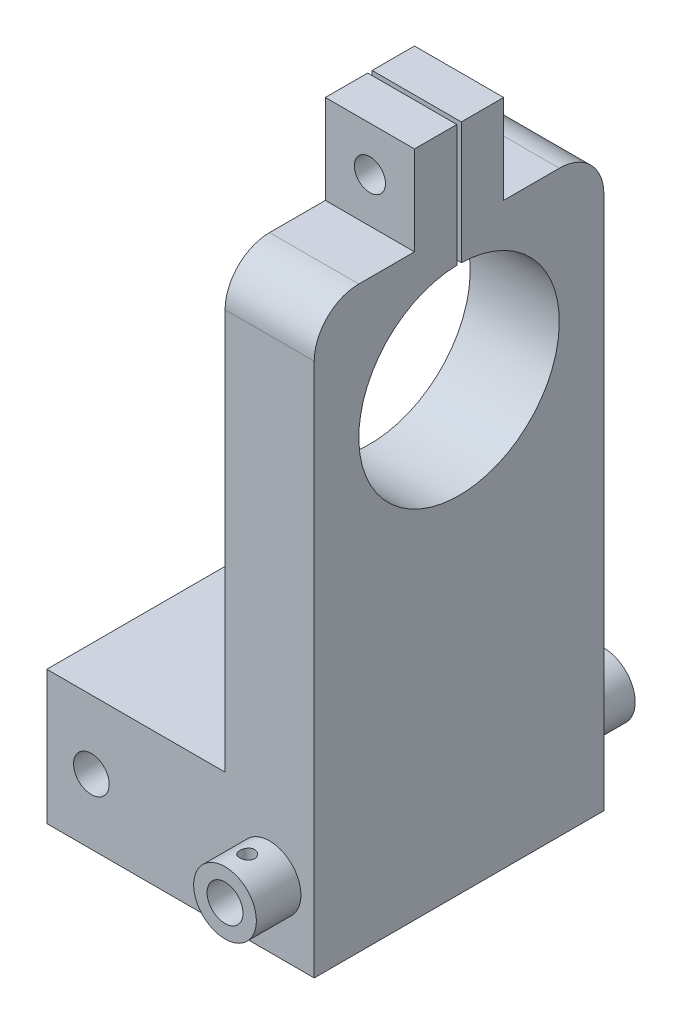
SolidWorks part; units mm, degrees
material "Aleación 6061"
ref_plane "Alzado" through (0, 0, 0) normal (0, 0, 1) x (1, 0, 0)
ref_plane "Planta" through (0, 0, 0) normal (0, 1, 0) x (1, 0, 0)
ref_plane "Vista lateral" through (0, 0, 0) normal (1, 0, 0) x (0, 0, -1)
sketch "Croquis1" plane through (0, 0, 0) normal (1, 0, 0) x (0, 0, -1)
  line L0 (0, 0) -> (0, 49.8635) construction
  line L2 (-32.5, 0) -> (-32.5, -100)
  line L3 (-32.5, -100) -> (32.5, -100)
  line L4 (32.5, 0) -> (32.5, -100)
  line L5 (-32.5, 0) -> (32.5, -100) construction
  line L6 (-32.5, -100) -> (32.5, 0) construction
  line L7 (-10, 49.8635) -> (10, 49.8635)
  line L8 (10, 49.8635) -> (10, 29.8635)
  line L9 (10, 29.8635) -> (22.5, 29.8635)
  line L10 (32.5, 19.8635) -> (32.5, 0)
  line L11 (-32.5, 19.8635) -> (-32.5, 0)
  line L12 (-10, 29.8635) -> (-22.5, 29.8635)
  line L13 (-10, 49.8635) -> (-10, 29.8635)
  circle A0 centre (0, 0) radius 22.5
  arc A3 (32.5, 19.8635) -> (22.5, 29.8635) centre (22.5, 19.8635) ccw
  arc A4 (-32.5, 19.8635) -> (-22.5, 29.8635) centre (-22.5, 19.8635) cw
  point P8 (0, -50)
  dimension "D1" = 100
  dimension "D2" = 10
  dimension "D3" = 45
  dimension "D4" = 10
  dimension "D5" = 20
extrude "Saliente-Extruir1" add sketch "Croquis1" along normal blind 20
sketch "Croquis2" plane through (0, 0, 0) normal (-1, 0, 0) x (0, 0, 1)
  line L0 (-32.5, -100) -> (-32.5, 19.8635) construction
  line L1 (32.5, -100) -> (-32.5, -100)
  line L2 (32.5, -100) -> (32.5, -70)
  line L3 (32.5, -70) -> (-32.5, -70)
  line L4 (-32.5, -100) -> (-32.5, -70)
  line L5 (32.5, -100) -> (-32.5, -70) construction
  line L6 (32.5, -70) -> (-32.5, -100) construction
  point P4 (0, -85)
  dimension "D1" = 30
extrude "Saliente-Extruir2" add sketch "Croquis2" along normal blind 40
sketch "Croquis4" plane through (0, 0, 0) normal (-1, 0, 0) x (0, 0, 1)
  line L1 (-0.5, 56.9278) -> (0.5, 56.9278)
  line L2 (-0.5, 56.9278) -> (-0.5, -3.0722)
  line L3 (-0.5, -3.0722) -> (0.5, -3.0722)
  line L4 (0.5, 56.9278) -> (0.5, -3.0722)
  line L5 (-0.5, 56.9278) -> (0.5, -3.0722) construction
  line L6 (-0.5, -3.0722) -> (0.5, 56.9278) construction
  point P0 (0, 26.9278)
  dimension "D1" = 1
  dimension "D2" = 60
extrude "Cortar-Extruir1" cut sketch "Croquis4" against normal blind 40
hole_wizard "Taladro de margen para M61" positions "Croquis3D1" profile "Croquis5" hole size "M6" standard "Ansi Metric" end condition through all
sketch3d "Croquis3D1"
  line L0 (20, 49.8635, -10) -> (0, 49.8635, -10) construction
  point P0 (10, 39.8635, -10)
  point P5 (10, 49.8635, -10)
  dimension "D1" = 10
sketch "Croquis5" plane through (10, 39.8635, -10) normal (1, 0, 0) x (0, 1, 0)
  line L0 (0, 0) -> (0, 42.5)
  line L1 (0, 42.5) -> (3.5, 42.5)
  line L2 (3.5, 42.5) -> (3.5, 0)
  line L5 (3.5, 0) -> (0, 0)
  line L11 (0, -6.35) -> (0, 107.95) construction
  dimension "Diámetro de taladro hasta el siguiente" = 7
  dimension "Profundidad de taladro hasta el siguiente" = 42.5
sketch "Croquis6" plane through (0, 0, -32.5) normal (0, 0, -1) x (-1, 0, 0)
  line L0 (10, -100) -> (10, -70) construction
  line L1 (-20, -100) -> (40, -100) construction
  line L2 (40, -70) -> (0, -70) construction
  circle A0 centre (30, -85.3671) radius 4
  circle A1 centre (-10, -85.3671) radius 4
  dimension "D1" = 20
  dimension "D2" = 8
extrude "Cortar-Extruir2" cut sketch "Croquis6" against normal through all
sketch "Croquis7" plane through (0, 0, 32.5) normal (0, 0, 1) x (1, 0, 0)
  circle A0 centre (9.9867, -85.397) radius 4.0327
  circle A1 centre (9.9867, -85.397) radius 7.0327
  dimension "D1" = 3
extrude "Saliente-Extruir3" add sketch "Croquis7" along normal blind 10 and the other way blind 75
hole_wizard "Perforador para roscar para macho de roscar para M4x0.71" positions "Croquis3D2" profile "Croquis9" hole size "M4x0.7" standard "Ansi Metric"
sketch3d "Croquis3D2"
  point P0 (9.9403, -78.3644, 37.5)
  point P2 (10.1188, -78.3655, -37.5)
  dimension "D1" = 5
  dimension "D2" = 5
sketch "Croquis9" plane through (9.9403, -78.3644, 37.5) normal (0, 0, 1) x (-1, -0.0066, 0)
  line L0 (0, 0) -> (0, 5.9914)
  line L1 (0, 5.9914) -> (1.65, 5)
  line L2 (1.65, 5) -> (1.65, 0)
  line L5 (1.65, 0) -> (0, 0)
  line L10 (0, 5.9914) -> (-1.65, 5) construction
  line L11 (0, -6.35) -> (0, 107.95) construction
  dimension "Diámetro de taladro" = 3.3
  dimension "Profundidad de taladro" = 5
  dimension "Ángulo de perforador" = 118
cosmetic thread "Rosca cosmética1" parameters "D2"=4
cosmetic thread "Rosca cosmética2" parameters "D2"=4
